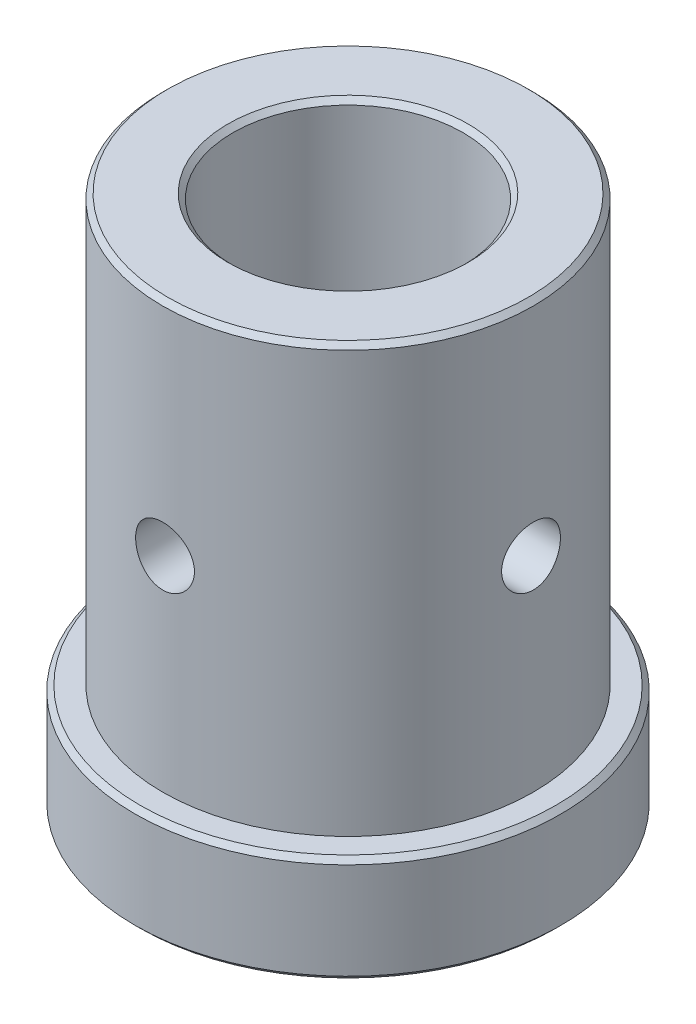
SolidWorks part; units mm, degrees
material "Nylon 101"
ref_plane "Front Plane" through (0, 0, 0) normal (0, 0, 1) x (1, 0, 0)
ref_plane "Top Plane" through (0, 0, 0) normal (0, 1, 0) x (1, 0, 0)
ref_plane "Right Plane" through (0, 0, 0) normal (1, 0, 0) x (0, 0, -1)
sketch "Sketch1" plane through (0, 0, 0) normal (0, 1, 0) x (1, 0, 0)
  circle A0 centre (0, 0) radius 11.049
  dimension "D1" = 22.098
extrude "Boss-Extrude1" add sketch "Sketch1" along normal blind 25.4
sketch "Sketch2" plane through (0, 0, 0) normal (0, -1, 0) x (1, 0, 0)
  circle A0 centre (0, 0) radius 12.7
  dimension "D1" = 25.4
extrude "Boss-Extrude2" add sketch "Sketch2" along normal blind 6.35
sketch "Sketch3" plane through (0, -6.35, 0) normal (0, -1, 0) x (1, 0, 0)
  circle A0 centre (0, 0) radius 6.858
  dimension "D1" = 13.716
extrude "Cut-Extrude1" cut sketch "Sketch3" against normal through all
sketch "Sketch4" plane through (0, -6.35, 0) normal (0, -1, 0) x (1, 0, 0)
  circle A0 centre (0, 0) radius 11.1125
  dimension "D1" = 22.225
ref_plane "Plane1" through (0, 9.525, 0) normal (0, 1, 0) x (1, 0, 0)
chamfer "Chamfer1" distance 0.3 angle 45 5 edges at (0, 0, -12.7) (0, -6.35, -12.7) (0, 25.4, 11.049) (0, 25.4, -6.858) (0, -6.35, -6.858)
sketch "Sketch5" plane through (0, 0, 0) normal (0, 0, 1) x (1, 0, 0)
  line L0 (12.4, 0) -> (-12.4, 0) construction
  circle A0 centre (0, 12.192) radius 1.7526
  dimension "D1" = 3.5052
  dimension "D2" = 12.192
extrude "Cut-Extrude2" cut sketch "Sketch5" against normal through all both and the other way through all
sketch "Sketch6" plane through (0, 0, 0) normal (1, 0, 0) x (0, 0, -1)
  line L0 (12.4, 0) -> (-12.4, 0) construction
  circle A0 centre (0, 12.192) radius 1.7526
  dimension "D1" = 3.5052
  dimension "D2" = 12.192
extrude "Cut-Extrude3" cut sketch "Sketch6" against normal through all both and the other way through all
equation "\"D1@Chamfer1\"=.3mm"
